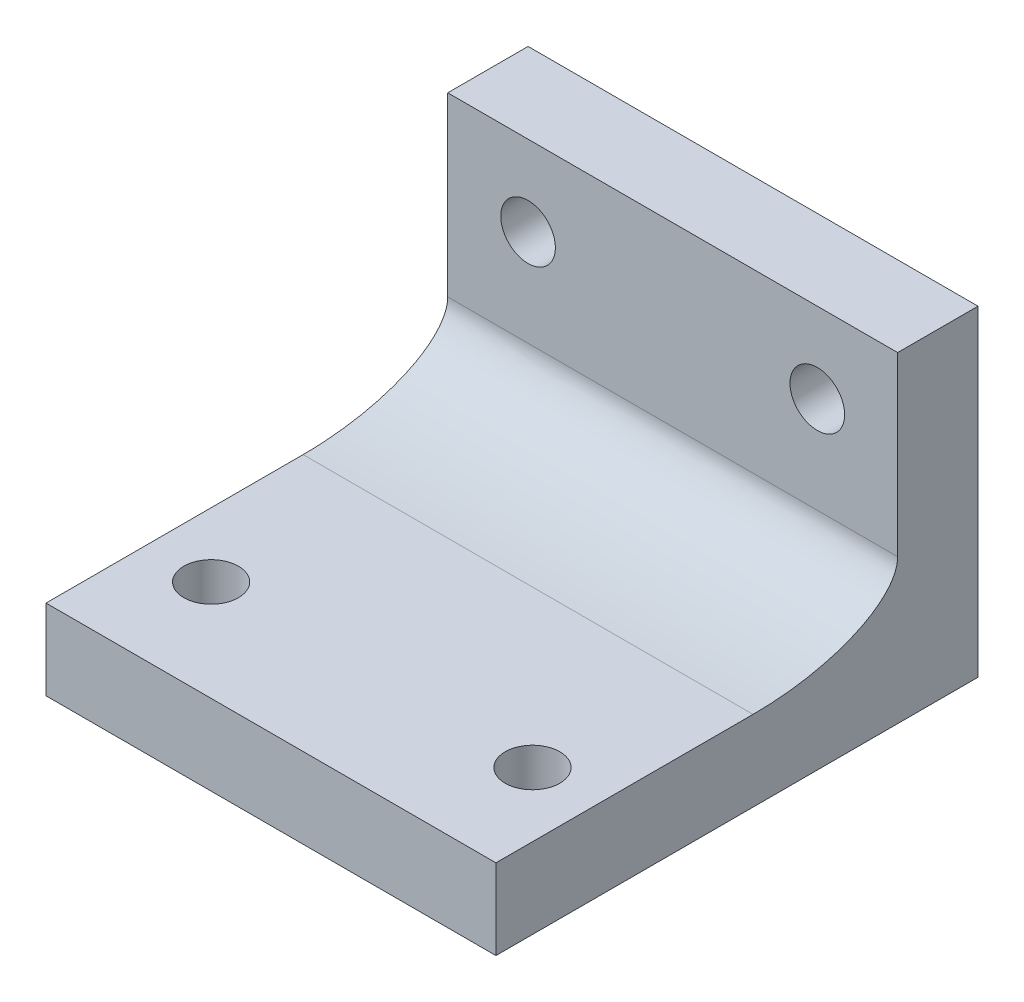
SolidWorks part; units mm, degrees
ref_plane "前视基准面" through (0, 0, 0) normal (0, 0, 1) x (1, 0, 0)
ref_plane "上视基准面" through (0, 0, 0) normal (0, 1, 0) x (1, 0, 0)
ref_plane "右视基准面" through (0, 0, 0) normal (1, 0, 0) x (0, 0, -1)
sketch "草图1" plane through (0, 0, 0) normal (0, 1, 0) x (1, 0, 0)
  line L1 (0, 0) -> (28, 0)
  line L2 (0, 0) -> (0, -30)
  line L3 (0, -30) -> (28, -30)
  line L4 (28, 0) -> (28, -30)
  dimension "D1" = 28
  dimension "D2" = 30
extrude "凸台-拉伸1" add sketch "草图1" along normal blind 5
sketch "草图2" plane through (0, 5, 0) normal (0, 1, 0) x (1, 0, 0)
  line L0 (28, -30) -> (28, 0) construction
  line L1 (0, 0) -> (28, 0)
  line L2 (0, 0) -> (0, -5)
  line L3 (0, -5) -> (28, -5)
  line L4 (28, 0) -> (28, -5)
  dimension "D1" = 5
extrude "凸台-拉伸2" add sketch "草图2" along normal blind 15
sketch "草图3" plane through (0, 5, 0) normal (0, 1, 0) x (1, 0, 0)
  line L0 (14, 0) -> (14, -30) construction
  line L1 (28, 0) -> (0, 0) construction
  line L2 (0, -30) -> (28, -30) construction
  circle A0 centre (4, -23.725) radius 1.7
  circle A1 centre (24, -23.725) radius 1.7
  dimension "D1" = 20
  dimension "D2" = 3.4
  dimension "D3" = 23.725
extrude "切除-拉伸1" cut sketch "草图3" against normal blind 5
sketch "草图4" plane through (0, 0, 5) normal (0, 0, 1) x (1, 0, 0)
  line L0 (14, 0) -> (14, 20) construction
  line L1 (0, 0) -> (28, 0) construction
  line L2 (0, 20) -> (28, 20) construction
  circle A0 centre (5, 15) radius 1.7
  circle A1 centre (23, 15) radius 1.7
  dimension "D2" = 3.4
  dimension "D3" = 15
  dimension "D1" = 18
extrude "切除-拉伸2" cut sketch "草图4" against normal blind 5
fillet "圆角1" radius 9 1 edges at (14, 5, 5) second distance 4 first distance on face at (4, 5, 25.425)
